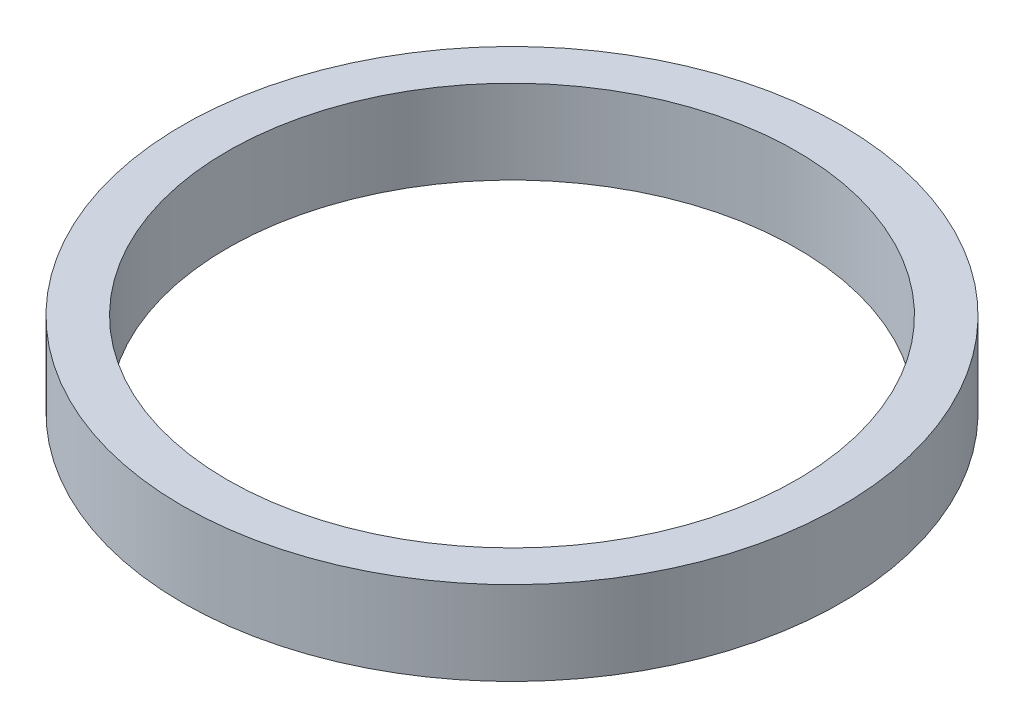
SolidWorks part; units mm, degrees
ref_plane "Front Plane" through (0, 0, 0) normal (0, 0, 1) x (1, 0, 0)
ref_plane "Top Plane" through (0, 0, 0) normal (0, 1, 0) x (1, 0, 0)
ref_plane "Right Plane" through (0, 0, 0) normal (1, 0, 0) x (0, 0, -1)
sketch "Sketch1" plane through (0, 0, 0) normal (0, 1, 0) x (1, 0, 0)
  circle A0 centre (0, 0) radius 55
  dimension "FLANGE_OD" = 110
extrude "Boss-Extrude1" add sketch "Sketch1" along normal blind 14
sketch "Sketch2" plane through (0, 0, 0) normal (0, 1, 0) x (1, 0, 0)
  circle A0 centre (0, 0) radius 47.5
  dimension "BORE_D" = 95
extrude "Cut-Extrude1" cut sketch "Sketch2" along normal through all
sketch "Sketch3" plane through (0, 14, 0) normal (0, 1, 0) x (1, 0, 0)
  circle A0 centre (0, 0) radius 25.2518 construction
  circle A1 centre (-25.2518, 0) radius 1.5
  dimension "BOLT_D" = 3
  dimension "BOLT_PCD" = 50.5035
extrude "Cut-Extrude2" cut sketch "Sketch3" against normal blind 10.4469 rebuild error yes
pattern_circular "CirPattern1" count 3 over 360 rebuild error yes
